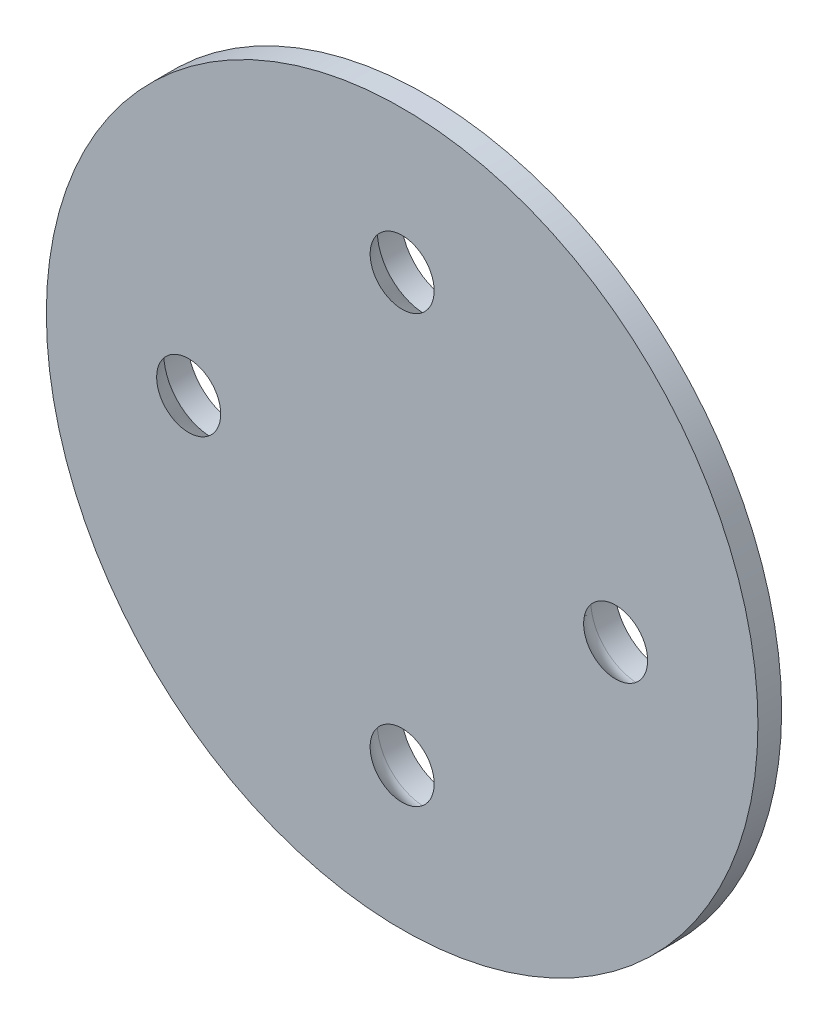
SolidWorks part; units mm, degrees
material "ABS"
ref_plane "正面" through (0, 0, 0) normal (0, 0, 1) x (1, 0, 0)
ref_plane "平面" through (0, 0, 0) normal (0, 1, 0) x (1, 0, 0)
ref_plane "右側面" through (0, 0, 0) normal (1, 0, 0) x (0, 0, -1)
sketch "ｽｹｯﾁ1" plane through (0, 0, 0) normal (0, 0, 1) x (1, 0, 0)
  circle A0 centre (0, 0) radius 15
  dimension "D1" = 30
extrude "ﾎﾞｽ - 押し出し1" add sketch "ｽｹｯﾁ1" along normal blind 1
sketch "ｽｹｯﾁ2" plane through (0, 0, 0) normal (0, 0, -1) x (-1, 0, 0)
  circle A0 centre (0, 0) radius 13
  dimension "D1" = 26
extrude "ﾎﾞｽ - 押し出し2" add sketch "ｽｹｯﾁ2" along normal blind 1
sketch "ｽｹｯﾁ3" plane through (0, 0, -1) normal (0, 0, -1) x (-1, 0, 0)
  circle A0 centre (9, 0) radius 2.05
  circle A1 centre (0, -9) radius 2.05
  circle A2 centre (-9, 0) radius 2.05
  circle A3 centre (0, 9) radius 2.05
  point P2 (-6.95, 0)
  point P4 (-9.6307, -17.1827)
  point P5 (0, -6.95)
  point P12 (0, 0)
  point P13 (6.95, 0)
  point P14 (0, 6.95)
  dimension "D1" = 4.1
  dimension "D2" = 9
  dimension "D3" = 4
extrude "ｶｯﾄ - 押し出し1" cut sketch "ｽｹｯﾁ3" against normal blind 1
sketch "ｽｹｯﾁ4" plane through (0, 0, 1) normal (0, 0, 1) x (1, 0, 0)
  circle A0 centre (-9, 0) radius 1.35
  circle A1 centre (0, 9) radius 1.35
  circle A2 centre (9, 0) radius 1.35
  circle A3 centre (0, -9) radius 1.35
  point P2 (7.65, 0)
  point P4 (16.8354, 18.714)
  point P5 (0, 7.65)
  point P12 (0, 0)
  point P13 (-7.65, 0)
  point P14 (0, -7.65)
  dimension "D1" = 2.7
  dimension "D2" = 9
  dimension "D3" = 4
loft "ｶｯﾄ - ﾛﾌﾄ2" cut section edge at (6.95, 0, 0) section "ｽｹｯﾁ4" start constraint normal to profile start tangent length 1 connector at (6.9624, -0.2248, 0) connector at (7.65, 0.0079, 1)
sketch "ｽｹｯﾁ5" plane through (0, 0, 1) normal (0, 0, 1) x (1, 0, 0)
  line L0 (0, 0) -> (9, 0) construction
loft "ｶｯﾄ - ﾛﾌﾄ3" cut section edge at (-2.05, -9, 0) section "ｽｹｯﾁ4<5>" start constraint normal to profile start tangent length 1 connector at (-0.0223, -6.9501, 0) connector at (-0.0219, -7.6502, 1)
sketch "ｽｹｯﾁ4<5>" plane through (0, 0, 1) normal (0, 0, 1) x (1, 0, 0) same geometry as "ｽｹｯﾁ4"
loft "ｶｯﾄ - ﾛﾌﾄ5" cut section edge at (-11.05, 0, 0) section "ｽｹｯﾁ4<6>" connector at (-6.95, -0.0077, 0) connector at (-7.6501, -0.0142, 1)
sketch "ｽｹｯﾁ4<6>" plane through (0, 0, 1) normal (0, 0, 1) x (1, 0, 0) same geometry as "ｽｹｯﾁ4"
loft "ｶｯﾄ - ﾛﾌﾄ6" cut section edge at (-2.05, 9, 0) section "ｽｹｯﾁ4<7>" connector at (-0.0237, 6.9501, 0) connector at (-0.0238, 7.6502, 1)
sketch "ｽｹｯﾁ4<7>" plane through (0, 0, 1) normal (0, 0, 1) x (1, 0, 0) same geometry as "ｽｹｯﾁ4"
sketch "ｽｹｯﾁ6" plane through (0, 0, -1) normal (0, 0, -1) x (-1, 0, 0)
  circle A0 centre (0, 0) radius 2
  dimension "D1" = 4
extrude "ﾎﾞｽ - 押し出し3" add sketch "ｽｹｯﾁ6" along normal blind 1.5
